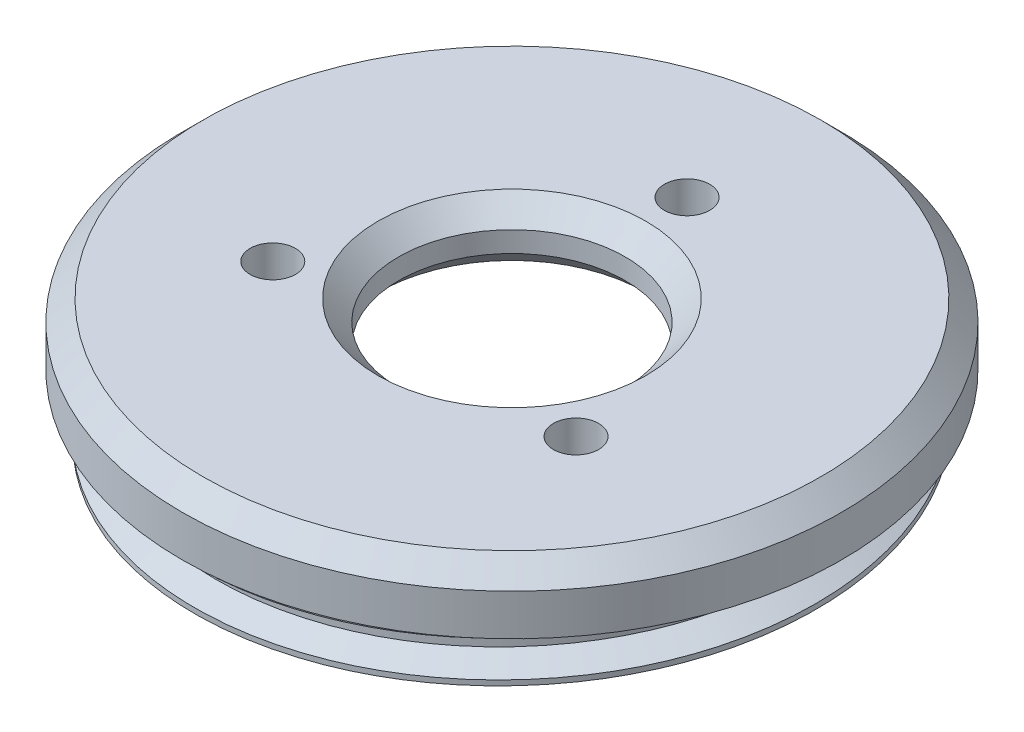
SolidWorks part; units mm, degrees
ref_plane "Спереди" through (0, 0, 0) normal (0, 0, 1) x (1, 0, 0)
ref_plane "Сверху" through (0, 0, 0) normal (0, 1, 0) x (1, 0, 0)
ref_plane "Справа" through (0, 0, 0) normal (1, 0, 0) x (0, 0, -1)
sketch "Эскиз1" plane through (0, 0, 0) normal (0, 1, 0) x (1, 0, 0)
  circle A0 centre (0, 0) radius 16
  circle A1 centre (0, 0) radius 8.5 construction
  circle A2 centre (0, 8.5) radius 1.1
  circle A3 centre (7.3612, -4.25) radius 1.1
  circle A4 centre (-7.3612, -4.25) radius 1.1
  circle A5 centre (0, 0) radius 5.5
  point P7 (0, 0)
  point P12 (0, 0)
  dimension "D1" = 32
  dimension "D2" = 17
  dimension "D3" = 2.2
  dimension "D5" = 11
  dimension "D4" = 3
extrude "Бобышка-Вытянуть1" add sketch "Эскиз1" along normal blind 3
sketch "Эскиз2" plane through (0, 0, 0) normal (0, -1, 0) x (1, 0, 0)
  circle A0 centre (0, 0) radius 13
  circle A1 centre (0, 0) radius 14
  dimension "D1" = 26
  dimension "D2" = 1
extrude "Бобышка-Вытянуть2" add sketch "Эскиз2" along normal blind 3
thread "Резьба1" pitch 2 method extrude trim with start face yes profile "Профиль резьбы1" start angle 0, offset 2, length 0, pitch 2, diameter 28
ref_plane "Плоскость1" through (14, -5, 0) normal (0, 0, 1) x (1, 0, 0)
sketch "Профиль резьбы1" plane through (14, -5, 0) normal (0, 0, 1) x (1, 0, 0)
  line L0 (0, 0) -> (0, 2) construction
  line L1 (0, 0) -> (1.0825, 0.625)
  line L2 (1.0825, 0.625) -> (1.0825, 0.875)
  line L3 (1.0825, 0.875) -> (0, 1.5)
  line L4 (1.0825, 0.75) -> (0, 0.75) construction
  line L11 (0, 0) -> (0, 1.5)
  point P2 (0, 0)
  dimension "Pitch" = 2
  dimension "Profile_Angle" = 60
  dimension "Profile_Land" = 0.25
  dimension "Profile_Height" = 1.0825
chamfer "Фаска1" distance 1 angle 45 5 edges at (0, 3, 16) (7.3612, 0, 5.35) (0, 0, -7.4) (-7.3612, 0, 5.35) (0, 3, 5.5)
chamfer "Фаска2" distance 1 angle 45 1 edges at (0, 0, 5.5)
equation "\"bearing_d1\"= 6'Bearing inner diameter"
equation "\"bearing_d2\"= 17'Bearing external diameter"
equation "\"bearing h\"= 6'Bearing heigh"
equation "\"pin_d\"= 2'Pin diameter"
equation "\"pin_h\"= 12'Pin heigh"
equation "\"print_offset\"= 0.2'Offset for printing holes"
equation "\"module_diameter\"= 41"
equation "\"D2@Эскиз1\"=8.5*2"
equation "\"D3@Эскиз1\"=\"print_offset\"+2"
equation "\"motor_diameter\"= 32"
equation "\"D1@Эскиз1\"=\"motor_diameter\""
equation "\"D1@Эскиз2\"=\"motor_diameter\"-6"
